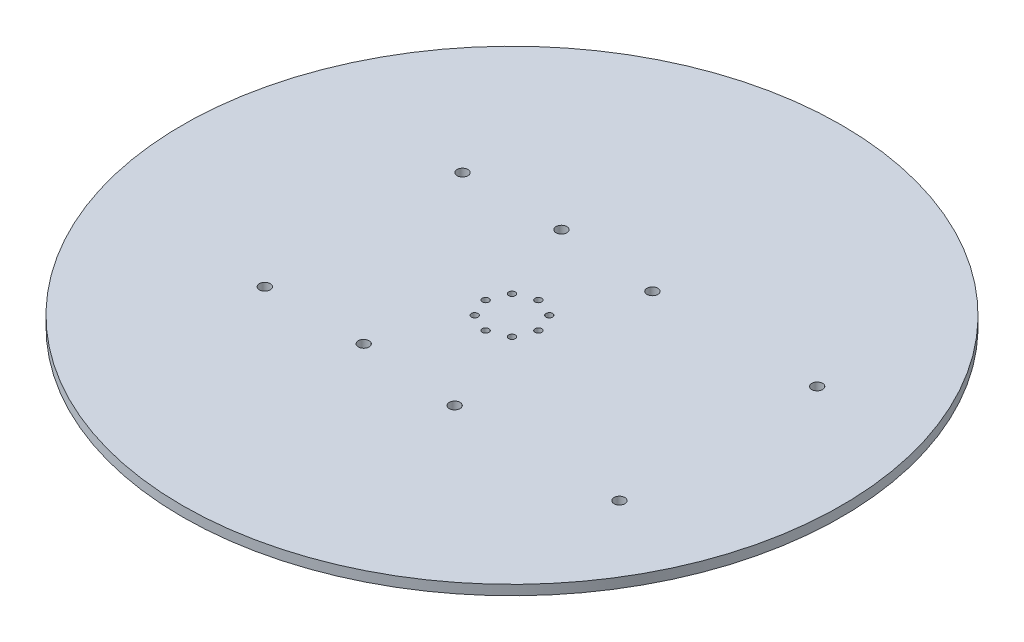
SolidWorks part; units mm, degrees
material "ABS"
ref_plane "Front Plane" through (0, 0, 0) normal (0, 0, 1) x (1, 0, 0)
ref_plane "Top Plane" through (0, 0, 0) normal (0, 1, 0) x (1, 0, 0)
ref_plane "Right Plane" through (0, 0, 0) normal (1, 0, 0) x (0, 0, -1)
sketch "Sketch2" plane through (0, 0, 0) normal (0, 1, 0) x (1, 0, 0)
  circle A0 centre (0, 0) radius 100
  dimension "D1" = 200
extrude "Boss-Extrude1" add sketch "Sketch2" along normal blind 3
sketch "Sketch3" plane through (0, 0, 0) normal (0, -1, 0) x (1, 0, 0)
  circle A0 centre (0, 75) radius 10
  dimension "D1" = 75
  dimension "D2" = 20
extrude "Boss-Extrude2" add sketch "Sketch3" along normal blind 4.75
sketch "Sketch4" plane through (0, 0, 0) normal (0, 0, 1) x (1, 0, 0)
  line L0 (0, 3) -> (0, -49997) construction
  line L1 (100, 3) -> (-100, 3) construction
  point P4 (0, 3)
pattern_circular "CirPattern1" count 5 over 360 about axis through (0, 3, 0) along (0, -1, 0) of "Boss-Extrude2"
fillet "Fillet3" radius 10 5 edges at (0, -4.75, 65) (61.8187, -4.75, 20.0861) (38.206, -4.75, -52.5861) (-38.206, -4.75, -52.5861) (-61.8187, -4.75, 20.0861)
sketch "Sketch5" plane through (0, 0, 0) normal (0, -1, 0) x (1, 0, 0)
  line L1 (-0.75, -9.5) -> (0.75, -9.5)
  line L2 (-0.75, -9.5) -> (-0.75, -12.5)
  line L3 (-0.75, -12.5) -> (0.75, -12.5)
  line L4 (0.75, -9.5) -> (0.75, -12.5)
  line L5 (-0.75, -9.5) -> (0.75, -12.5) construction
  line L6 (-0.75, -12.5) -> (0.75, -9.5) construction
  circle A0 centre (0, 0) radius 11
  circle A1 centre (0, 8) radius 1
  circle A2 centre (5.6569, 5.6569) radius 1
  circle A3 centre (8, 0) radius 1
  circle A4 centre (5.6569, -5.6569) radius 1
  circle A5 centre (0, -8) radius 1
  circle A6 centre (-5.6569, -5.6569) radius 1
  circle A7 centre (-8, 0) radius 1
  circle A8 centre (-5.6569, 5.6569) radius 1
  point P5 (0, -11)
  point P22 (0, 0)
  dimension "D1" = 22
  dimension "D2" = 2
  dimension "D3" = 8
  dimension "D5" = 8
  dimension "D6" = 1.5
  dimension "D7" = 3
  dimension "D4" = 8
extrude "Cut-Extrude1" cut sketch "Sketch5" against normal up to surface (3 mm away) contours A8 | A1 | A2 | A3 | A4 | A5 | A6 | A7 up to face at (0, 3, 100)
extrude "Boss-Extrude3" add sketch "Sketch5<3>" along normal blind 3 contours L2 A0 L4 L1 | A0 L2 L3 L4 region at (0, 0, -10.2458) region at (0, 0, -11.7457)
sketch "Sketch5<3>" plane through (0, 0, 0) normal (0, -1, 0) x (1, 0, 0) same geometry as "Sketch5"
sketch "Sketch6" plane through (0, 3, 0) normal (0, 1, 0) x (1, 0, 0)
  line L1 (-45, 30) -> (-15, 30)
  line L2 (-45, 30) -> (-45, -30)
  line L3 (-45, -30) -> (-15, -30)
  line L4 (-15, 30) -> (-15, -30)
  circle A0 centre (-45, 30) radius 2
  circle A1 centre (-15, 30) radius 2
  circle A2 centre (-15, -30) radius 2
  circle A3 centre (-45, -30) radius 2
  point P4 (-15, 0)
  dimension "D4" = 4
  dimension "D1" = 30
  dimension "D2" = 60
  dimension "D3" = 15
  dimension "D5" = 2
  dimension "D6" = 2
hole_wizard "Tap Drill for M4x0.7 Tap1" positions "3DSketch1" profile "Sketch7" hole size "M4x0.7" standard "ANSI Metric" end condition up to next
sketch3d "3DSketch1"
  point P0 (-45, 3, -30)
  point P3 (-15, 3, -30)
  point P6 (-45, 3, 30)
  point P9 (-15, 3, 30)
sketch "Sketch7" plane through (-45, 3, -30) normal (1, 0, 0) x (0, 0, 1)
  line L0 (0, 0) -> (0, 3)
  line L1 (0, 3) -> (1.65, 3)
  line L2 (1.65, 3) -> (1.65, 0)
  line L5 (1.65, 0) -> (0, 0)
  line L11 (0, -6.35) -> (0, 107.95) construction
  dimension "Thru Hole Dia." = 3.3
  dimension "Thru Hole Depth" = 3
sketch "Sketch8" plane through (0, 3, 0) normal (0, 1, 0) x (1, 0, 0)
  line L5 (-15, 30) -> (-15, -30) construction
  line L7 (15, 27.6) -> (65, 27.6)
  line L8 (15, 27.6) -> (15, -32.4)
  line L9 (15, -32.4) -> (65, -32.4)
  line L10 (65, 27.6) -> (65, -32.4)
  line L13 (-45, 30) -> (-15, 30) construction
  line L14 (13.9, -16) -> (65, -16)
  line L15 (13.9, -13.75) -> (13.9, -18.25) construction
  circle A0 centre (15, 27.6) radius 2
  circle A1 centre (65, 27.6) radius 2
  circle A2 centre (15, -32.4) radius 2
  circle A3 centre (65, -32.4) radius 2
  dimension "D4" = 4
  dimension "D5" = 4
  dimension "D6" = 4
  dimension "D7" = 4
  dimension "D1" = 50
  dimension "D2" = 60
  dimension "D3" = 30
  dimension "D8" = 2.4
  dimension "D9" = 2.9021
hole_wizard "Tap Drill for M4x0.7 Tap2" positions "3DSketch2" profile "Sketch9" hole size "M4x0.7" standard "ANSI Metric" end condition up to next
sketch3d "3DSketch2"
  point P0 (15, 3, -27.6)
  point P3 (15, 3, 32.4)
  point P6 (65, 3, 32.4)
  point P9 (65, 3, -27.6)
sketch "Sketch9" plane through (15, 3, -27.6) normal (1, 0, 0) x (0, 0, 1)
  line L0 (0, 0) -> (0, 3)
  line L1 (0, 3) -> (1.65, 3)
  line L2 (1.65, 3) -> (1.65, 0)
  line L5 (1.65, 0) -> (0, 0)
  line L11 (0, -6.35) -> (0, 107.95) construction
  dimension "Thru Hole Dia." = 3.3
  dimension "Thru Hole Depth" = 3
